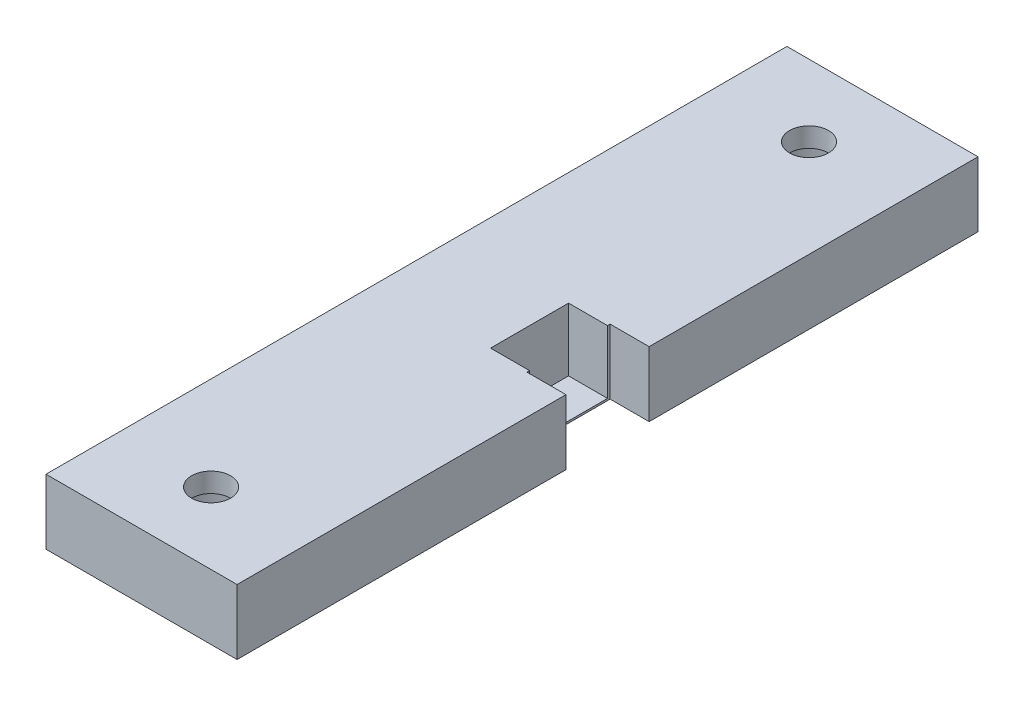
SolidWorks part; units mm, degrees
ref_plane "Front" through (0, 0, 0) normal (0, 0, 1) x (1, 0, 0)
ref_plane "Top" through (0, 0, 0) normal (0, 1, 0) x (1, 0, 0)
ref_plane "Right" through (0, 0, 0) normal (1, 0, 0) x (0, 0, -1)
sketch "草图2" plane through (0, 0, 0) normal (0, 1, 0) x (1, 0, 0)
  line L0 (-22.4307, -42.4706) -> (-1.4307, -42.4706)
  line L1 (-22.4307, -42.4706) -> (-22.4307, 14.5294)
  line L2 (-22.4307, 14.5294) -> (-1.4307, 14.5294)
  line L3 (-1.4307, 14.5294) -> (-1.4307, -42.4706)
extrude "凸台-拉伸1" add sketch "草图2" along normal blind 5 contours L3 L0 L1 L2
sketch "草图3" plane through (0, 5, 0) normal (0, 1, 0) x (1, 0, 0)
  line L0 (-1.4307, -42.4706) -> (-1.4307, -31.4706)
  line L1 (-1.4307, 14.5294) -> (-1.4307, -42.4706) construction
  line L2 (-1.4307, -31.4706) -> (-22.4307, -42.4706)
  circle A0 centre (-11.9307, -36.9706) radius 1.5
extrude "切除-拉伸1" cut sketch "草图3" against normal blind 5 contours L2 A0 | L2 A0 region at (-11.6353, 5, 37.5345) region at (-12.2261, 5, 36.4066)
sketch "草图4" plane through (0, 5, 0) normal (0, 1, 0) x (1, 0, 0)
  line L0 (-22.4307, 14.5294) -> (-22.4307, 3.5294)
  line L1 (-22.4307, -42.4706) -> (-22.4307, 14.5294) construction
  line L2 (-22.4307, 3.5294) -> (-1.4307, 14.5294)
  circle A0 centre (-11.9307, 9.0294) radius 1.5
extrude "切除-拉伸2" cut sketch "草图4" against normal blind 5 contours L2 A0 | L2 A0 region at (-12.2261, 5, -9.5934) region at (-11.6353, 5, -8.4655)
sketch "草图5" plane through (0, 0, 0) normal (0, -1, 0) x (1, 0, 0)
  circle A0 centre (-11.9307, -9.0294) radius 3.5
extrude "切除-拉伸3" cut sketch "草图5" against normal blind 3.5
sketch "草图6" plane through (0, 0, 0) normal (0, -1, 0) x (1, 0, 0)
  circle A0 centre (-11.9307, 36.9706) radius 3.5
extrude "切除-拉伸4" cut sketch "草图6" against normal blind 3.5
ref_plane "基准面1" through (-22.4307, 0, 42.4706) normal (1, 0, 0) x (0, 0, -1)
sketch "草图8" plane through (0, 5, 0) normal (0, 1, 0) x (1, 0, 0)
  line L0 (-22.4307, 14.5294) -> (-19.4307, 14.5294)
  line L1 (-22.4307, 14.5294) -> (-1.4307, 14.5294) construction
  line L2 (-19.4307, 14.5294) -> (-19.4307, -42.4706)
  line L3 (-22.4307, -42.4706) -> (-1.4307, -42.4706) construction
  line L4 (-19.4307, -42.4706) -> (-22.4307, -42.4706)
  line L5 (-22.4307, -42.4706) -> (-22.4307, 14.5294)
  line L6 (-11.9307, 14.5294) -> (-11.9307, -42.4706) construction
  line L7 (-4.4307, -42.4706) -> (-1.4307, -42.4706)
  line L8 (-4.4307, 14.5294) -> (-4.4307, -42.4706)
  line L9 (-1.4307, 14.5294) -> (-4.4307, 14.5294)
  line L10 (-1.4307, -42.4706) -> (-1.4307, 14.5294)
extrude "切除-拉伸5" cut sketch "草图8" against normal blind 5
sketch "草图10" plane through (0, 5, 0) normal (0, 1, 0) x (1, 0, 0)
  line L0 (-19.4307, -13.9706) -> (-4.4307, -13.9706) construction
  line L1 (-19.4307, -42.4706) -> (-19.4307, 14.5294) construction
  line L2 (-4.4307, 14.5294) -> (-4.4307, -42.4706) construction
  line L3 (-4.4307, -13.9706) -> (-4.4307, -10.9706)
  line L4 (-4.4307, -10.9706) -> (-7.4307, -10.9706)
  line L5 (-7.4307, -10.9706) -> (-7.4307, -16.9706)
  line L6 (-7.4307, -16.9706) -> (-4.4307, -16.9706)
  line L7 (-4.4307, -16.9706) -> (-4.4307, -13.9706)
extrude "切除-拉伸7" cut sketch "草图10" against normal blind 5 contours L7 L3 L4 L5 L6
sketch "草图11" plane through (0, 0, 0) normal (0, -1, 0) x (1, 0, 0)
  line L0 (-19.4307, 13.9706) -> (-7.4307, 13.9706) construction
  line L1 (-19.4307, 42.4706) -> (-19.4307, -14.5294) construction
  line L2 (-7.4307, 10.9706) -> (-7.4307, 16.9706) construction
  line L3 (-19.4307, 13.9706) -> (-19.4307, 1.4706)
  line L4 (-19.4307, 1.4706) -> (-4.4307, 1.4706)
  line L6 (-4.4307, -14.5294) -> (-4.4307, 10.9706) construction
  line L8 (-19.4307, 42.4706) -> (-19.1307, 42.4706)
  line L9 (-19.4307, 42.4706) -> (-4.4307, 42.4706) construction
  line L10 (-19.1307, 42.4706) -> (-19.1307, -14.5294)
  line L11 (-19.4307, -14.5294) -> (-4.4307, -14.5294) construction
  line L12 (-19.1307, -14.5294) -> (-19.4307, -14.5294)
  line L13 (-19.4307, -14.5294) -> (-19.4307, 42.4706)
  line M3 (-4.4307, 42.4706) -> (-19.4307, 42.4706)
  line M4 (-19.4307, 42.4706) -> (-19.4307, -14.5294)
extrude "切除-拉伸8" cut sketch "草图11" against normal blind 5 contours L0 L10 M4 M3 region at (-19.2807, 0, 28.2206)
sketch "草图12" plane through (0, 0, 0) normal (0, -1, 0) x (-1, 0, 0)
  line L0 (19.4307, -13.9706) -> (19.4307, 14.5294)
  line L1 (19.4307, 14.5294) -> (19.1307, 14.5294)
  line L2 (19.4307, 14.5294) -> (4.4307, 14.5294) construction
  line L3 (19.1307, 14.5294) -> (19.1307, -13.9706)
  line L4 (19.1307, -13.9706) -> (19.4307, -13.9706)
extrude "切除-拉伸9" cut sketch "草图12" against normal blind 10
sketch "草图13" plane through (0, 0, 0) normal (0, -1, 0) x (1, 0, 0)
  line L0 (-4.4307, 10.9706) -> (-4.4307, 10.7706)
  line L1 (-4.4307, -14.5294) -> (-4.4307, 10.9706) construction
  line L2 (-4.4307, 10.7706) -> (-7.4307, 10.7706)
  line L3 (-7.4307, 10.7706) -> (-7.4307, 10.9706)
  line L4 (-7.4307, 10.9706) -> (-4.4307, 10.9706)
  line L5 (-7.4307, 16.9706) -> (-4.4307, 16.9706)
  line L7 (-7.4307, 16.9706) -> (-7.4307, 17.1706)
  line L8 (-4.4307, 16.9706) -> (-4.4307, 17.1706)
  line L9 (-4.4307, 16.9706) -> (-4.4307, 42.4706) construction
  line L10 (-4.4307, 17.1706) -> (-7.4307, 17.1706)
  line M11 (-4.4307, -14.5294) -> (-4.4307, 10.9706)
  line M12 (-4.4307, 10.9706) -> (-7.4307, 10.9706)
extrude "切除-拉伸10" cut sketch "草图13" against normal blind 10 contours L3 L2 M11 M12 | L4 L0 L2 L3 | L5 L8 L10 L7 region at (-5.9307, 0, 10.8706)
sketch "草图9" plane through (0, 5, 0) normal (0, 1, 0) x (1, 0, 0)
  line L0 (-19.4307, -13.9706) -> (-4.4307, -13.9706) construction
  line L1 (-19.4307, -42.4706) -> (-19.4307, 14.5294) construction
  line L2 (-4.4307, 14.5294) -> (-4.4307, -10.7706) construction
  line L3 (-4.4307, -13.9706) -> (-4.4307, -10.9706)
  line L4 (-4.4307, -10.9706) -> (-10.4307, -10.9706)
  line L5 (-10.4307, -10.9706) -> (-10.4307, -16.9706)
  line L6 (-10.4307, -16.9706) -> (-4.4307, -16.9706)
  line L7 (-4.4307, -16.9706) -> (-4.4307, -13.9706)
extrude "切除-拉伸6" cut sketch "草图9" against normal blind 4.85
